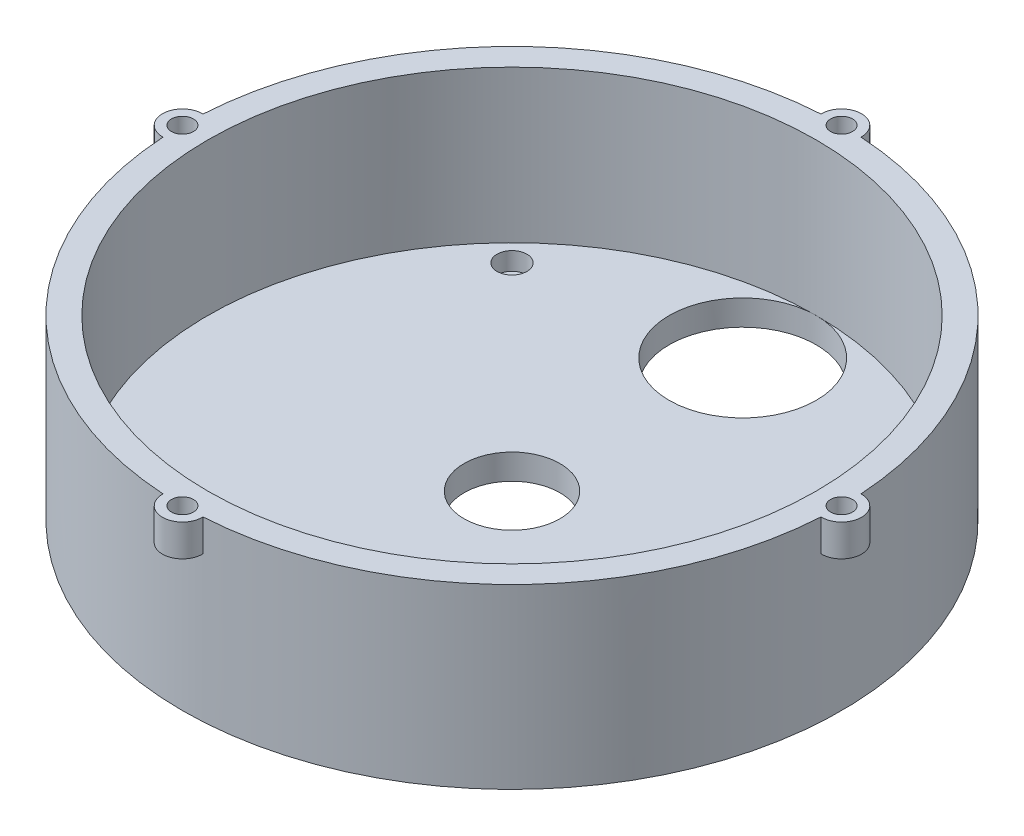
SolidWorks part; units mm, degrees
ref_plane "Front Plane" through (0, 0, 0) normal (0, 0, 1) x (1, 0, 0)
ref_plane "Top Plane" through (0, 0, 0) normal (0, 1, 0) x (1, 0, 0)
ref_plane "Right Plane" through (0, 0, 0) normal (1, 0, 0) x (0, 0, -1)
sketch "Sketch1" plane through (0, 0, 0) normal (0, 1, 0) x (1, 0, 0)
  line L0 (0, 0) -> (-17.4549, 51.9165) construction
  line L1 (0, 0) -> (17.4549, 51.9165) construction
  line L2 (0, 82.55) -> (49.1964, 82.55) construction
  circle A0 centre (0, 0) radius 76.2
  circle A1 centre (0, 0) radius 82.55
  circle A2 centre (0, 57.785) radius 18.415
  circle A3 centre (0, 0) radius 12
  dimension "D1" = 152.4
  dimension "D2" = 165.1
  dimension "D3" = 24
  dimension "D4" = 36.83
extrude "Boss-Extrude1" add sketch "Sketch1" against normal blind 6.35 contours A0 A3 | A1 A0 region at (-52.3575, 0, 52.3575) region at (-80.2151, 0, 0)
extrude "Boss-Extrude2" add sketch "Sketch1<3>" along normal blind 38.1 contours A1 A0 region at (-80.2151, 0, 0)
sketch "Sketch1<3>" plane through (0, 0, 0) normal (0, 1, 0) x (1, 0, 0) same geometry as "Sketch1"
sketch "Sketch5" plane through (0, 0, 0) normal (0, 1, 0) x (1, 0, 0)
  circle A0 centre (-49.53, -49.53) radius 3.75
  circle A1 centre (-49.53, 49.53) radius 3.75
  circle A2 centre (49.53, 49.53) radius 3.75
  circle A3 centre (49.53, -49.53) radius 3.75
  circle A4 centre (-49.53, 49.53) radius 2.25
  circle A5 centre (49.53, 49.53) radius 2.25
  circle A6 centre (49.53, -49.53) radius 2.25
  circle A7 centre (-49.53, -49.53) radius 2.25
  point P6 (0, 0)
  point P13 (0, 0)
  point P16 (0, 0)
  point P21 (0, 0)
  point P23 (0, 0)
  dimension "D1" = 7.5
  dimension "D4" = 4.5
  dimension "D3" = 99.06
  dimension "D2" = 4
  dimension "D5" = 4
extrude "Cut-Extrude1" cut sketch "Sketch5" against normal blind 4.5 contours A1 A4 | A2 A5 | A3 A6 | A0 A7 region at (-53.1739, 0, 49.53) region at (-53.1739, 0, -49.53) region at (45.8861, 0, -49.53) region at (45.8861, 0, 49.53)
extrude "Cut-Extrude2" cut sketch "Sketch5<4>" against normal blind 12.7 contours A7 | A6 | A5 | A4 region at (-49.53, 0, -49.53) region at (49.53, 0, -49.53) region at (49.53, 0, 49.53) region at (-49.53, 0, 49.53)
sketch "Sketch5<4>" plane through (0, 0, 0) normal (0, 1, 0) x (1, 0, 0) same geometry as "Sketch5"
sketch "Sketch6" plane through (0, 38.1, 0) normal (0, 1, 0) x (1, 0, 0)
  circle A0 centre (-82.55, 0) radius 2.75
  circle A1 centre (0, 0) radius 82.55 construction
  circle A2 centre (-82.55, 0) radius 5
  circle A3 centre (0, 82.55) radius 2.75
  circle A4 centre (0, 82.55) radius 5
  circle A5 centre (82.55, 0) radius 2.75
  circle A6 centre (82.55, 0) radius 5
  circle A7 centre (0, -82.55) radius 2.75
  circle A8 centre (0, -82.55) radius 5
  point P17 (0, 0)
  circle M4 centre (0, 0) radius 82.55
  dimension "D1" = 5.5
  dimension "D2" = 10
  dimension "D3" = 4
extrude "Boss-Extrude3" add sketch "Sketch6" against normal blind 8 contours A2 A0 M4 | A0 M4 | A2 A0 M4 | A8 A7 M4 | A8 A7 M4 | A5 M4 | A5 M4 | A6 A5 M4 | A6 A5 M4 | A3 M4 | A3 M4 | A4 A3 M4 | A4 A3 M4 | A0 M4 | A7 region at (-81.3747, 38.1, 0) region at (-80.5098, 38.1, -2.0065) region at (-83.7088, 38.1, 0) region at (-85.4125, 38.1, 0) region at (-3.8688, 38.1, -82.3476) region at (-0.074, 38.1, -87.437) region at (-3.8793, 38.1, 82.5714) region at (0, 38.1, 77.6616) region at (0, 38.1, -81.3747) region at (0, 38.1, -83.7088) region at (82.3476, 38.1, -3.8688) region at (85.9533, 38.1, -3.5079) region at (81.3747, 38.1, 0) region at (83.7088, 38.1, 0)
extrude "Cut-Extrude3" cut sketch "Sketch6<3>" against normal blind 7 contours A0 M4 | A0 M4 | A7 M4 | A7 M4 | A5 M4 | A5 M4 | A3 M4 | A3 M4 region at (-81.3747, 38.1, 0) region at (-83.7088, 38.1, 0) region at (0, 38.1, -81.3747) region at (0, 38.1, -83.7088) region at (0, 38.1, 83.7088) region at (0, 38.1, 81.3747) region at (81.3747, 38.1, 0) region at (83.7088, 38.1, 0)
sketch "Sketch6<3>" plane through (0, 38.1, 0) normal (0, 1, 0) x (1, 0, 0) same geometry as "Sketch6"
